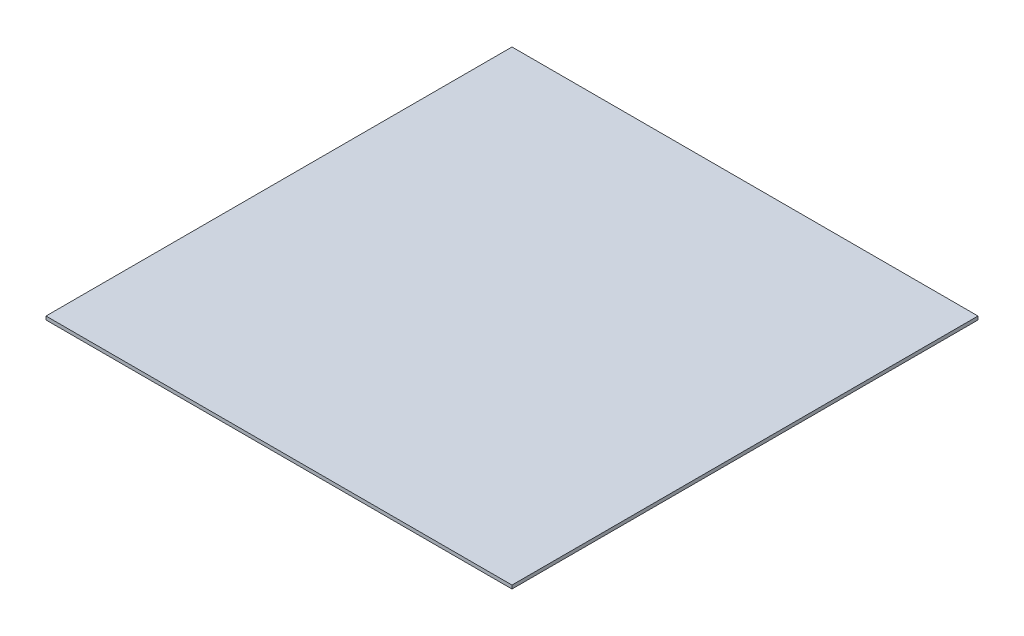
SolidWorks part; units mm, degrees
material "6061 Alloy"
ref_plane "Front Plane" through (0, 0, 0) normal (0, 0, 1) x (1, 0, 0)
ref_plane "Top Plane" through (0, 0, 0) normal (0, 1, 0) x (1, 0, 0)
ref_plane "Right Plane" through (0, 0, 0) normal (1, 0, 0) x (0, 0, -1)
sketch "Sketch1" plane through (0, 0, 0) normal (0, 1, 0) x (1, 0, 0)
  line L1 (-257.175, 257.175) -> (257.175, 257.175)
  line L2 (-257.175, 257.175) -> (-257.175, -257.175)
  line L3 (-257.175, -257.175) -> (257.175, -257.175)
  line L4 (257.175, 257.175) -> (257.175, -257.175)
  line L5 (-257.175, 257.175) -> (257.175, -257.175) construction
  line L6 (-257.175, -257.175) -> (257.175, 257.175) construction
  point P0 (0, 0)
  dimension "D1" = 514.35
extrude "Boss-Extrude1" add sketch "Sketch1" along normal blind 3.82
ref_axis "Axis2" through (0, 0, 257.175) along (0, 0, -1)
sketch "Sketch2" plane through (0, 3.82, 0) normal (0, 1, 0) x (1, 0, 0)
  circle A0 centre (0, 0) radius 17.5
  dimension "D1" = 35
